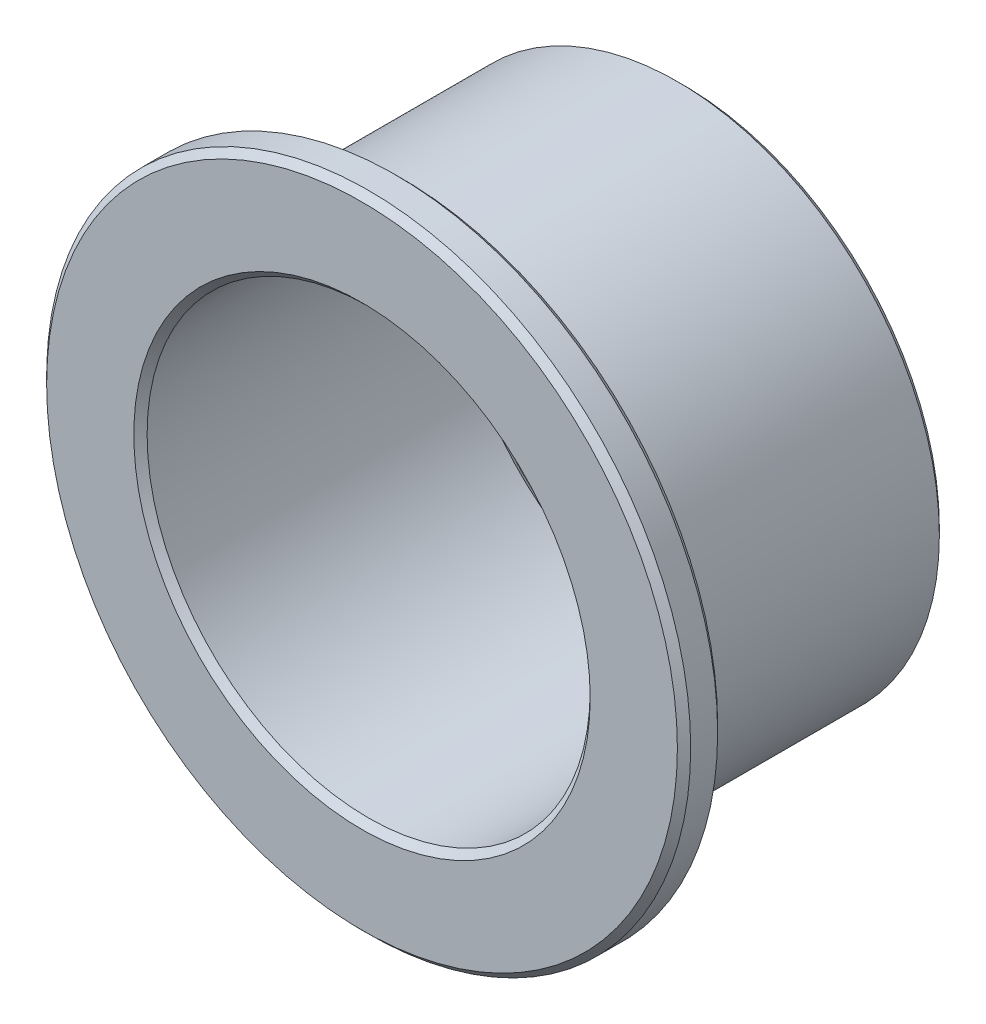
SolidWorks part; units mm, degrees
material "Manganese Bronze"
ref_plane "Front" through (0, 0, 0) normal (0, 0, 1) x (1, 0, 0)
ref_plane "Top" through (0, 0, 0) normal (0, 1, 0) x (1, 0, 0)
ref_plane "Right" through (0, 0, 0) normal (1, 0, 0) x (0, 0, -1)
sketch "Sketch1" plane through (0, 0, 0) normal (0, 0, 1) x (1, 0, 0)
  circle A0 centre (0, 0) radius 17.4752
  circle A1 centre (0, 0) radius 20.6629
  circle A2 centre (0, 0) radius 25.4
  dimension "ID" = 34.9504
  dimension "OD" = 41.3258
  dimension "Flange OD" = 50.8
sketch "Sketch2" plane through (0, 0, 0) normal (1, 0, 0) x (0, 0, -1)
  line L0 (-12.7, -25.4) -> (12.7, -25.4) construction
  line L1 (0, 25.4) -> (0, -25.4) construction
  line L3 (-9.525, 20.6629) -> (12.7, 20.6629) construction
  point P3 (0, -25.4)
  point P7 (0, 20.6629)
  point P9 (-9.525, -25.4)
  point P10 (-12.7, 25.4)
  point P23 (0, 25.4)
  dimension "Flange Thickness" = 3.175
  dimension "Length" = 25.4
sketch "Sketch3" plane through (0, 0, 0) normal (0, 0, 1) x (1, 0, 0)
  circle A0 centre (0, 0) radius 25.4 construction
  circle A1 centre (0, 0) radius 25.4
  circle A2 centre (0, 0) radius 17.4752 construction
  circle A3 centre (0, 0) radius 17.4752
extrude "Boss-Extrude1" add sketch "Sketch3" against normal up to vertex (-9.525 mm away) from vertex up to point (0, -25.4, 9.525) starting at point (0, -25.4, 12.7)
sketch "Sketch4" plane through (0, 0, 0) normal (0, 0, 1) x (1, 0, 0)
  circle A0 centre (0, 0) radius 17.4752 construction
  circle A1 centre (0, 0) radius 20.6629 construction
  circle A2 centre (0, 0) radius 17.4752
  circle A3 centre (0, 0) radius 20.6629
extrude "Boss-Extrude2" add sketch "Sketch4" against normal up to vertex (12.7 mm away) from vertex up to point (0, 20.6629, -12.7) starting at point (0, -25.4, 9.525)
chamfer "Chamfer1" distance 0.5243 angle 45 6 edges at (17.4752, 0, 12.7) (25.4, 0, 12.7) (25.4, 0, 9.525) (20.6629, 0, 9.525) (17.4752, 0, -12.7) (20.6629, 0, -12.7)
equation "\"D1@Chamfer1\"=\"ID@Sketch1\"*0.015"
